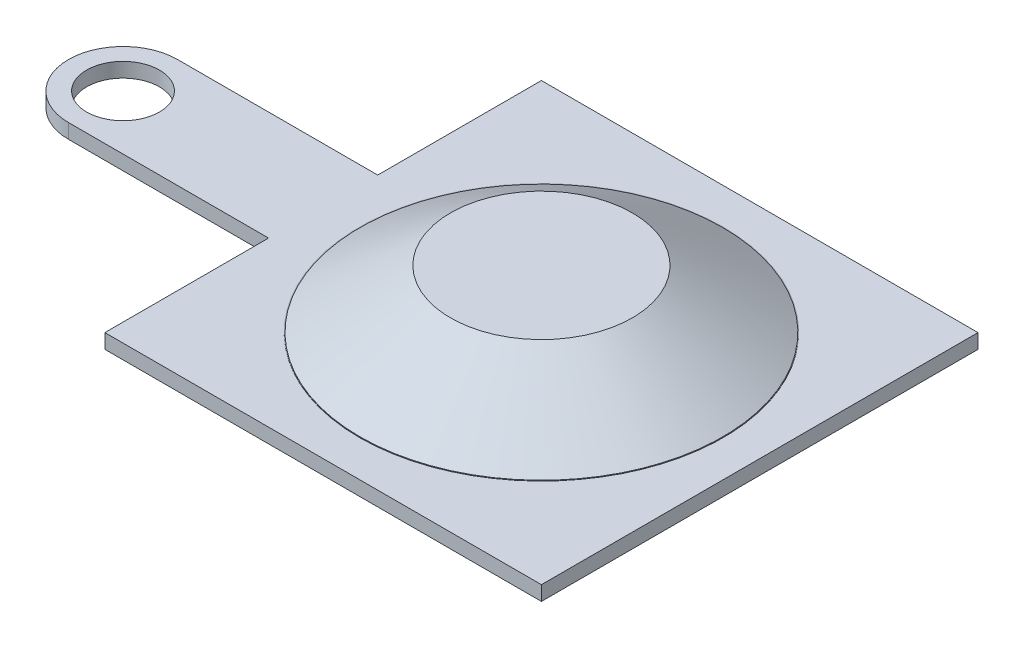
SolidWorks part; units mm, degrees
ref_plane "前视基准面" through (0, 0, 0) normal (0, 0, 1) x (1, 0, 0)
ref_plane "上视基准面" through (0, 0, 0) normal (0, 1, 0) x (1, 0, 0)
ref_plane "右视基准面" through (0, 0, 0) normal (1, 0, 0) x (0, 0, -1)
other "Configuration Table"
sketch "草图1" plane through (0, 0, 0) normal (0, 1, 0) x (1, 0, 0)
  line L1 (-6, -6) -> (6, -6)
  line L2 (-6, -6) -> (-6, 6)
  line L3 (-6, 6) -> (6, 6)
  line L4 (6, -6) -> (6, 6)
  line L5 (-6, -6) -> (6, 6) construction
  line L6 (-6, 6) -> (6, -6) construction
  line L7 (-6, 1.5) -> (-13, 1.5)
  line L8 (-6, 1.5) -> (-6, -1.5)
  line L9 (-6, -1.5) -> (-13, -1.5)
  line L10 (-13, 1.5) -> (-13, -1.5)
  circle A0 centre (0, 0) radius 5
  circle A1 centre (0, 0) radius 2.5
  circle A2 centre (-11.5, 0) radius 1
  point P12 (-13, 0)
  dimension "D1" = 10
  dimension "D2" = 5
  dimension "D7" = 2
  dimension "D3" = 12
  dimension "D4" = 3
  dimension "D5" = 7
  dimension "D6" = 1.5
extrude "凸台-拉伸1" add sketch "草图1" along normal blind 0.4 contours L1 L4 L3 L2 | L7 L10 L9 L8 | A2
extrude "凸台-拉伸2" add sketch "草图1<5>" along normal blind 1.6 from surface contours A1 starting at face at (-4.75, 0.4, 0)
sketch "草图1<5>" plane through (0, 0, 0) normal (0, 1, 0) x (1, 0, 0) same geometry as "草图1"
extrude "凸台-拉伸3" add sketch "草图1<6>" along normal blind 0.01 from surface contours A0 starting at face at (0, 0.4, -2.5)
sketch "草图1<6>" plane through (0, 0, 0) normal (0, 1, 0) x (1, 0, 0) same geometry as "草图1"
loft "放样1" add section edge at (0, 2, -2.5) section edge at (0, 0.4, -5) connector at (-2.2492, 2, 1.0914) connector at (-4.7108, 0.4, 1.6759)
fillet "圆角1" radius 1.5 2 edges at (-13, 0.2, 1.5) (-13, 0.2, -1.5)
